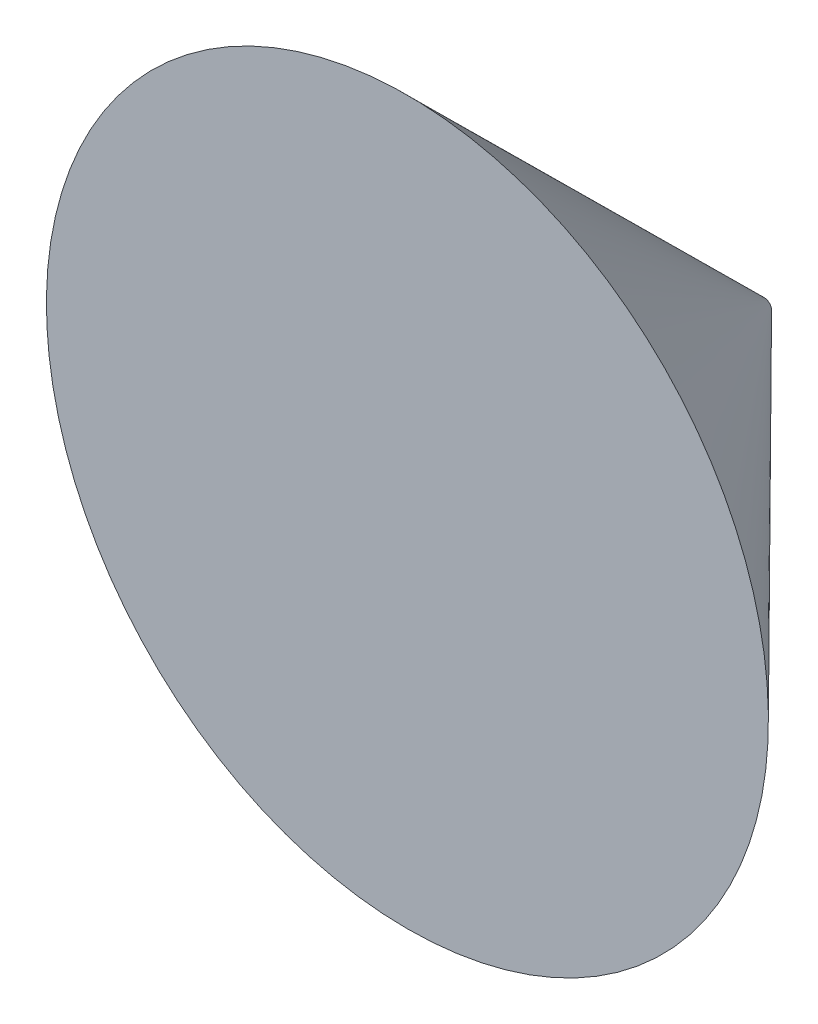
SolidWorks part; units mm, degrees
ref_plane "Front Plane" through (0, 0, 0) normal (0, 0, 1) x (1, 0, 0)
ref_plane "Top Plane" through (0, 0, 0) normal (0, 1, 0) x (1, 0, 0)
ref_plane "Right Plane" through (0, 0, 0) normal (1, 0, 0) x (0, 0, -1)
ref_axis "X" through (-88.99, 0, 0) along (1, 0, 0)
ref_axis "Y" through (0, 55, 0) along (0, -1, 0)
ref_axis "Z" through (0, 0, -88.99) along (0, 0, 1)
sketch "Sketch1" plane through (0, 0, 0) normal (1, 0, 0) x (0, 0, -1)
  line L0 (0, 0) -> (-196, 0)
  line L1 (-196, 0) -> (-196, 198.297)
  line L2 (-196, 198.297) -> (0, 4)
  line L3 (0, 4) -> (0, 0)
  dimension "D1" = 196
  dimension "D2" = 4
  dimension "D3" = 44.75
revolve "Revolve1" add sketch "Sketch1" angle 360 about L0
